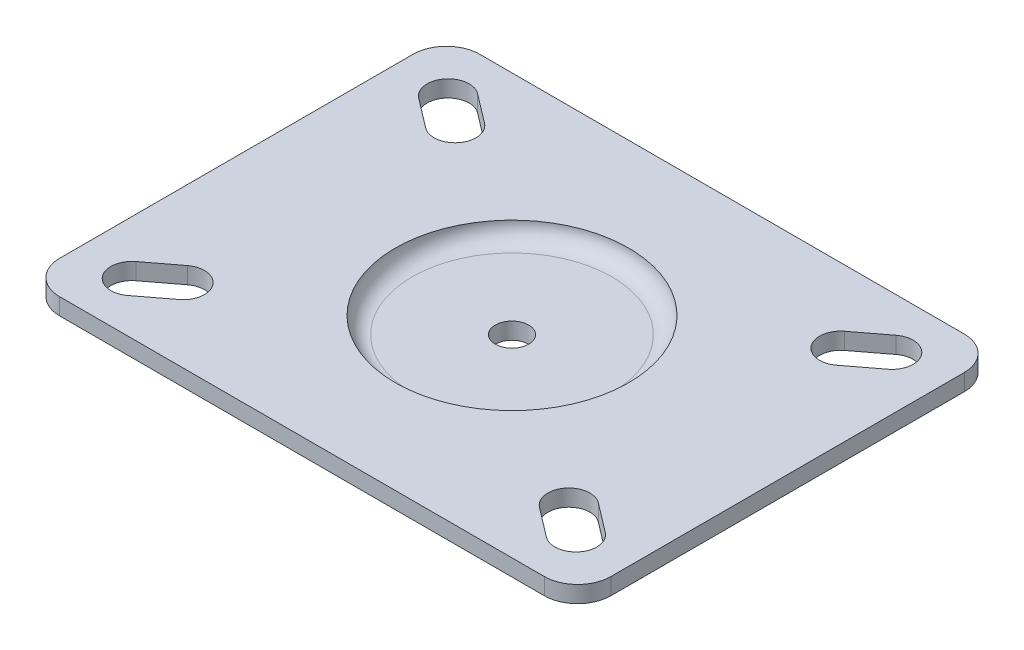
SolidWorks part; units mm, degrees
ref_plane "Front Plane" through (0, 0, 0) normal (0, 0, 1) x (1, 0, 0)
ref_plane "Top Plane" through (0, 0, 0) normal (0, 1, 0) x (1, 0, 0)
ref_plane "Right Plane" through (0, 0, 0) normal (1, 0, 0) x (0, 0, -1)
sketch "Sketch12" plane through (0, 0, 0) normal (0, 1, 0) x (-1, 0, 0)
  line L0 (52.5, 0) -> (0, 0) construction
  line L1 (-52.5, 40) -> (52.5, 40)
  line L2 (-52.5, 40) -> (-52.5, -40)
  line L3 (-52.5, -40) -> (52.5, -40)
  line L4 (52.5, 40) -> (52.5, -40)
  line L5 (-52.5, -40) -> (52.5, 40) construction
  dimension "D1" = 80
  dimension "D2" = 105
extrude "Boss-Extrude6" add sketch "Sketch12" along normal blind 3.175 separate body
sketch "Sketch15" plane through (0, 3.175, 0) normal (0, 1, 0) x (1, 0, 0)
  circle A0 centre (0, 0) radius 25.4
extrude "Boss-Extrude7" add sketch "Sketch15" against normal blind 6.35
sketch "Sketch16" plane through (0, 3.175, 0) normal (0, 1, 0) x (1, 0, 0)
  circle A0 centre (0, 0) radius 22.225
extrude "Cut-Extrude3" cut sketch "Sketch16" against normal blind 3.175
sketch "Sketch14" plane through (0, 3.175, 0) normal (0, 1, 0) x (-1, 0, 0)
  line L0 (52.5, 40) -> (-52.5, 40) construction
  line L2 (-42.284, 0) -> (42.284, 0) construction
  line L5 (0, 36.6967) -> (0, -39.6953) construction
  line L6 (42.284, 30.1212) -> (36.716, 25.8788) construction
  line L7 (44.7082, 26.9394) -> (39.1402, 22.6971)
  line L8 (39.8598, 33.3029) -> (34.2918, 29.0606)
  line L9 (-42.284, 30.1212) -> (-36.716, 25.8788) construction
  line L10 (-44.7082, 26.9394) -> (-39.1402, 22.6971)
  line L11 (-39.8598, 33.3029) -> (-34.2918, 29.0606)
  line L12 (-42.284, -30.1212) -> (-36.716, -25.8788) construction
  line L13 (-44.7082, -26.9394) -> (-39.1402, -22.6971)
  line L14 (-39.8598, -33.3029) -> (-34.2918, -29.0606)
  line L15 (42.284, -30.1212) -> (36.716, -25.8788) construction
  line L16 (44.7082, -26.9394) -> (39.1402, -22.6971)
  line L17 (39.8598, -33.3029) -> (34.2918, -29.0606)
  arc A0 (44.7082, 26.9394) -> (39.8598, 33.3029) centre (42.284, 30.1212) ccw
  arc A1 (34.2918, 29.0606) -> (39.1402, 22.6971) centre (36.716, 25.8788) ccw
  circle A2 centre (0, 0) radius 3.175
  arc A3 (-44.7082, 26.9394) -> (-39.8598, 33.3029) centre (-42.284, 30.1212) cw
  arc A4 (-34.2918, 29.0606) -> (-39.1402, 22.6971) centre (-36.716, 25.8788) cw
  arc A5 (-44.7082, -26.9394) -> (-39.8598, -33.3029) centre (-42.284, -30.1212) ccw
  arc A6 (-34.2918, -29.0606) -> (-39.1402, -22.6971) centre (-36.716, -25.8788) ccw
  arc A7 (44.7082, -26.9394) -> (39.8598, -33.3029) centre (42.284, -30.1212) cw
  arc A8 (34.2918, -29.0606) -> (39.1402, -22.6971) centre (36.716, -25.8788) cw
  point P6 (-39.5, -28)
  point P18 (39.5, 28)
  point P25 (-39.5, 28)
  point P33 (39.5, -28)
  dimension "D3" = 79
  dimension "D1" = 8
  dimension "D2" = 7
  dimension "D4" = 12
extrude "Cut-Extrude2" cut sketch "Sketch14" against normal up to next
fillet "Fillet6" radius 6.35 4 edges at (-52.5, 1.5875, 40) (-52.5, 1.5875, -40) (52.5, 1.5875, 40) (52.5, 1.5875, -40)
fillet "Fillet7" radius 3.175 2 edges at (0, -3.175, 25.4) (0, 0, 22.225)
